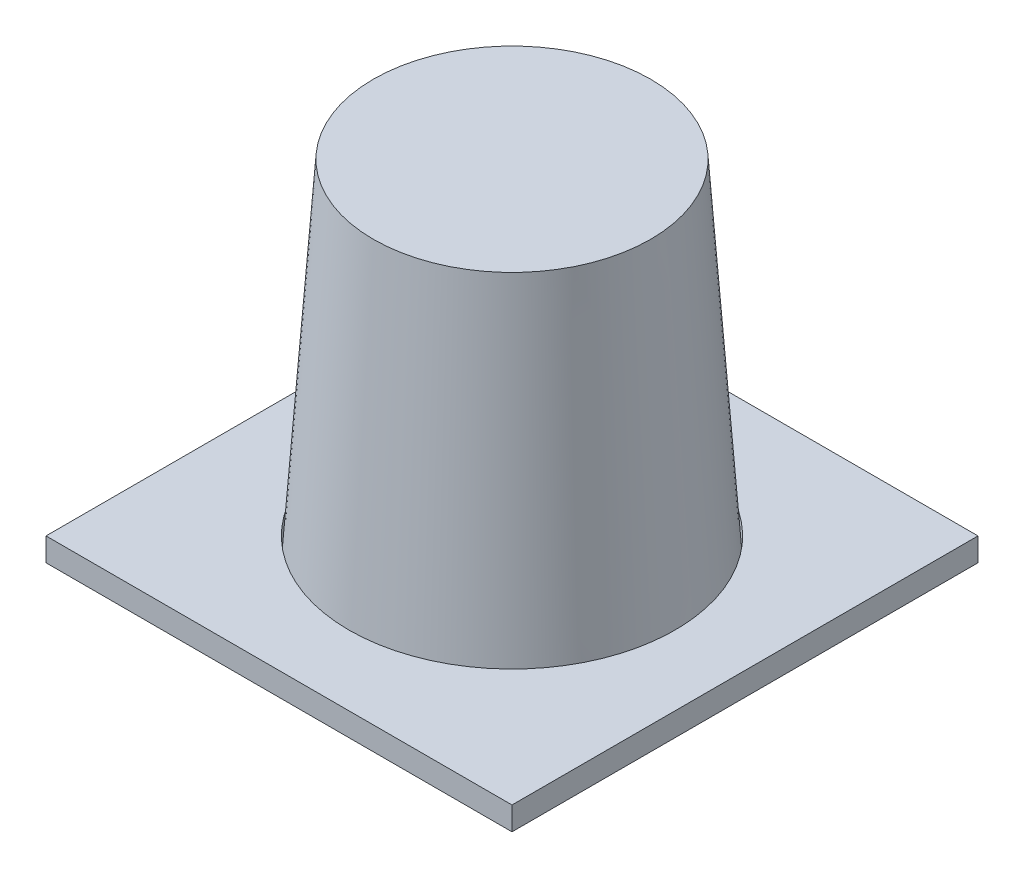
SolidWorks part; units mm, degrees
ref_plane "Front" through (0, 0, 0) normal (0, 0, 1) x (1, 0, 0)
ref_plane "Top" through (0, 0, 0) normal (0, 1, 0) x (1, 0, 0)
ref_plane "Right" through (0, 0, 0) normal (1, 0, 0) x (0, 0, -1)
other "Configuration Table"
sketch "Sketch1" plane through (0, 0, 0) normal (0, 1, 0) x (1, 0, 0)
  line L1 (-20, 20) -> (20, 20)
  line L2 (-20, 20) -> (-20, -20)
  line L3 (-20, -20) -> (20, -20)
  line L4 (20, 20) -> (20, -20)
  line L5 (-20, 20) -> (20, -20) construction
  line L6 (-20, -20) -> (20, 20) construction
  circle A0 centre (0, 0) radius 14
  point P0 (0, 0)
  dimension "D2" = 28
  dimension "D1" = 40
extrude "Boss-Extrude1" add sketch "Sketch1" along normal blind 30 draft 4 contours A0 region at (0, 0, 0)
extrude "Boss-Extrude2" add sketch "Sketch1<3>" along normal blind 2
sketch "Sketch1<3>" plane through (0, 0, 0) normal (0, 1, 0) x (1, 0, 0) same geometry as "Sketch1"
